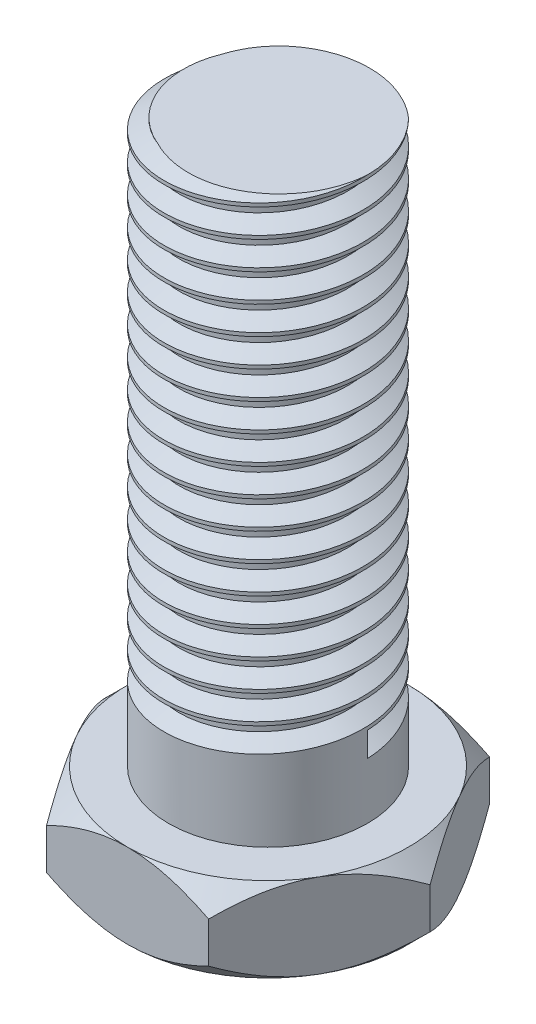
SolidWorks part; units mm, degrees
ref_plane "Front Plane" through (0, 0, 0) normal (0, 0, 1) x (1, 0, 0)
ref_plane "Top Plane" through (0, 0, 0) normal (0, 1, 0) x (1, 0, 0)
ref_plane "Right Plane" through (0, 0, 0) normal (1, 0, 0) x (0, 0, -1)
sketch "Sketch1" plane through (0, 0, 0) normal (0, 1, 0) x (1, 0, 0)
  line L1 (2.8868, 0) -> (1.4434, 2.5)
  line L2 (1.4434, 2.5) -> (-1.4434, 2.5)
  line L3 (-1.4434, 2.5) -> (-2.8868, 0)
  line L4 (-2.8868, 0) -> (-1.4434, -2.5)
  line L5 (-1.4434, -2.5) -> (1.4434, -2.5)
  line L6 (1.4434, -2.5) -> (2.8868, 0)
  circle A1 centre (0, 0) radius 2.5 construction
  dimension "D1" = 5
extrude "Boss-Extrude1" add sketch "Sketch1" along normal mid plane 1.5
sketch "Sketch2" plane through (0, 0.75, 0) normal (0, 1, 0) x (1, 0, 0)
  line L0 (1.4434, 2.5) -> (-1.4434, 2.5) construction
  circle A0 centre (0, 0) radius 2.5
extrude "Cut-Extrude2" cut sketch "Sketch2" against normal through all draft 45 flip side to cut
mirror "Mirror1" about plane through (0, 0, 0) normal (0, 1, 0) of "Cut-Extrude2" second plane through (0, 0, 0) second plane normal (0, 0, 1)
sketch "Sketch3" plane through (0, 0.75, 0) normal (0, 1, 0) x (1, 0, 0)
  circle A0 centre (0, 0) radius 1.77
  dimension "D1" = 3.54
extrude "Boss-Extrude2" add sketch "Sketch3" along normal blind 10
thread "Thread1" pitch 0.5 method cut profile "Thread Profile1" start angle 0, offset 1, length 0, pitch 0.5, diameter 3.54
ref_plane "Plane1" through (1.77, 1.75, 0) normal (0, 0, 1) x (1, 0, 0)
sketch "Thread Profile1" plane through (1.77, 1.75, 0) normal (0, 0, 1) x (1, 0, 0)
  line L0 (0, 0) -> (0, 0.5) construction
  line L11 (0, 0) -> (0, 0.4375)
  line L12 (0, 0.4375) -> (-0.2706, 0.2812)
  line L13 (-0.2706, 0.2812) -> (-0.2706, 0.1562)
  line L15 (-0.2706, 0.1562) -> (0, 0)
  line L17 (-0.2706, 0.2187) -> (0, 0.2187) construction
  point P2 (0, 0)
  dimension "Pitch" = 0.5
  dimension "Profile_Angle" = 60
  dimension "Profile_Land" = 0.125
  dimension "Profile_Height" = 0.2706
equation "\"Bolt shaft dia\"= 3.54mm"
equation "\"bolt head dia\"= 5mm"
equation "\"bolt head thickness\"= 1.5mm"
equation "\"Bolt shaft length\"= 10mm"
equation "\"D1@Sketch1\"=\"bolt head dia\""
equation "\"D1@Boss-Extrude1\"=\"bolt head thickness\""
equation "\"D1@Sketch3\"=\"Bolt shaft dia\""
equation "\"D1@Boss-Extrude2\"=\"Bolt shaft length\""
